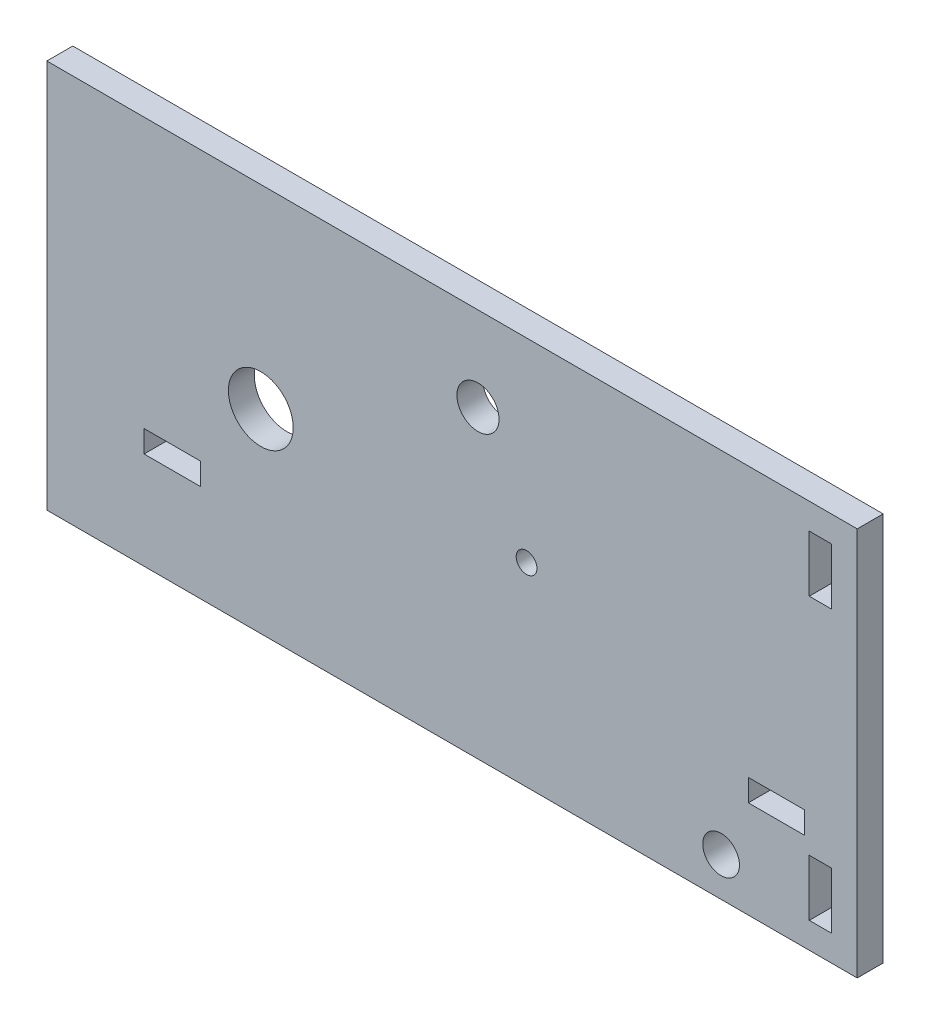
SolidWorks part; units mm, degrees
ref_plane "Front Plane" through (0, 0, 0) normal (0, 0, 1) x (1, 0, 0)
ref_plane "Top Plane" through (0, 0, 0) normal (0, 1, 0) x (1, 0, 0)
ref_plane "Right Plane" through (0, 0, 0) normal (1, 0, 0) x (0, 0, -1)
sketch "Sketch1" plane through (0, 0, 0) normal (0, 0, 1) x (1, 0, 0)
  line L1 (-79, -30) -> (42, -30)
  line L2 (-79, -30) -> (-79, 30)
  line L3 (-79, 30) -> (42, 30)
  line L4 (42, -30) -> (42, 30)
  line L5 (-64, -11.6) -> (-55.3, -11.6)
  line L6 (-64, -11.6) -> (-64, -15)
  line L7 (-64, -15) -> (-55.3, -15)
  line L8 (-55.3, -11.6) -> (-55.3, -15)
  line L9 (29.2, -11.6) -> (37.9, -11.6)
  line L10 (29.2, -11.6) -> (29.2, -15)
  line L11 (29.2, -15) -> (37.9, -15)
  line L12 (37.9, -11.6) -> (37.9, -15)
  circle A2 centre (-46, 0) radius 5
  circle A3 centre (-12.5, 17) radius 3.25
  circle A4 centre (25, -24) radius 2.83
  circle A5 centre (-5, 0) radius 1.6
  point P1 (0, 0)
  point P22 (-55.3, -13.3)
  point P24 (-79, 0)
  dimension "D3" = 15
  dimension "D4" = 121
  dimension "D5" = 33
  dimension "D6" = 8.7
  dimension "D7" = 33.5
  dimension "D10" = 6.5
  dimension "D12" = 104
  dimension "D13" = 6
  dimension "D14" = 5.66
  dimension "D15" = 54.5
  dimension "D18" = 41
  dimension "D19" = 17
  dimension "D20" = 10
  dimension "D21" = 10
  dimension "D2" = 60
  dimension "D8" = 3.4
  dimension "D9" = 15
  dimension "D11" = 15
  dimension "D16" = 84.5
extrude "Boss-Extrude1" add sketch "Sketch1" along normal blind 4
sketch "Sketch2" plane through (0, 0, 0) normal (0, 0, 1) x (1, 0, 0)
  line L0 (42, 30) -> (46, 30)
  line L1 (46, 30) -> (46, -30)
  line L2 (46, -30) -> (42, -30)
  line L13 (-79, -30) -> (42, -30) construction
  line L14 (42, -30) -> (42, 30)
  dimension "D1" = 4
extrude "Boss-Extrude2" add sketch "Sketch2" along normal blind 4
sketch "Sketch3" plane through (0, 0, 0) normal (0, 0, 1) x (1, 0, 0)
  line L0 (46, -30) -> (46, 30) construction
  line L1 (38.6, 26) -> (42, 26)
  line L2 (38.6, 26) -> (38.6, 17.3)
  line L3 (38.6, 17.3) -> (42, 17.3)
  line L4 (42, 26) -> (42, 17.3)
  line L5 (38.6, -17.3) -> (42, -17.3)
  line L6 (38.6, -17.3) -> (38.6, -26)
  line L7 (38.6, -26) -> (42, -26)
  line L8 (42, -17.3) -> (42, -26)
  line L9 (46, 30) -> (-79, 30) construction
  line L10 (-79, -30) -> (46, -30) construction
  dimension "D1" = 4
  dimension "D2" = 3.4
  dimension "D3" = 8.7
  dimension "D4" = 4
  dimension "D5" = 4
extrude "Cut-Extrude2" cut sketch "Sketch3" along normal through all both
equation "\"padding\"=4"
equation "\"hole_width\"=3.4"
equation "\"hole_height\"=8.7"
equation "\"D1@Sketch3\"=\"padding\""
equation "\"D2@Sketch3\"=\"hole_width\""
equation "\"D3@Sketch3\"=\"hole_height\""
equation "\"D4@Sketch3\"=\"padding\""
equation "\"D5@Sketch3\"=\"padding\""
